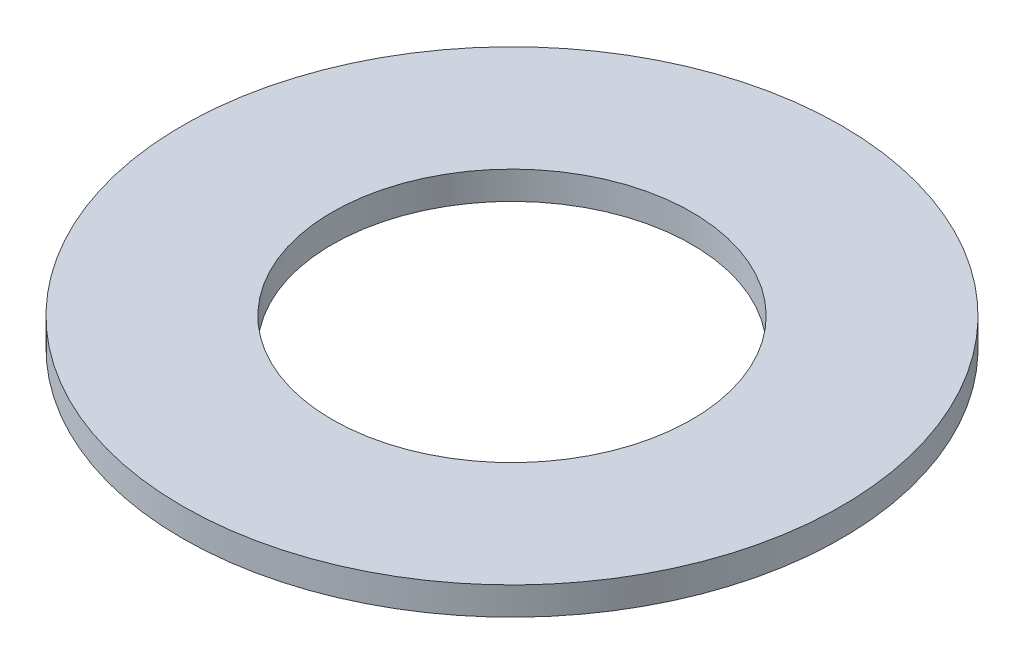
SolidWorks part; units mm, degrees
ref_plane "Front Plane" through (0, 0, 0) normal (0, 0, 1) x (1, 0, 0)
ref_plane "Top Plane" through (0, 0, 0) normal (0, 1, 0) x (1, 0, 0)
ref_plane "Right Plane" through (0, 0, 0) normal (1, 0, 0) x (0, 0, -1)
sketch "Sketch1" plane through (0, 0, 0) normal (0, 1, 0) x (1, 0, 0)
  circle A0 centre (0, 0) radius 82.5
  dimension "FLANGE_OD" = 165
extrude "Boss-Extrude1" add sketch "Sketch1" along normal blind 7
sketch "Sketch2" plane through (0, 0, 0) normal (0, 1, 0) x (1, 0, 0)
  circle A0 centre (0, 0) radius 45
  dimension "BORE_D" = 90
extrude "Cut-Extrude1" cut sketch "Sketch2" along normal through all
sketch "Sketch3" plane through (0, 7, 0) normal (0, 1, 0) x (1, 0, 0)
  circle A0 centre (0, 0) radius 33.6119 construction
  circle A1 centre (-33.6119, 0) radius 6.6934
  dimension "BOLT_D" = 13.3869
  dimension "BOLT_PCD" = 67.2239
extrude "Cut-Extrude2" cut sketch "Sketch3" against normal blind 5.2509 rebuild error yes
pattern_circular "CirPattern1" count 6 over 360 rebuild error yes
